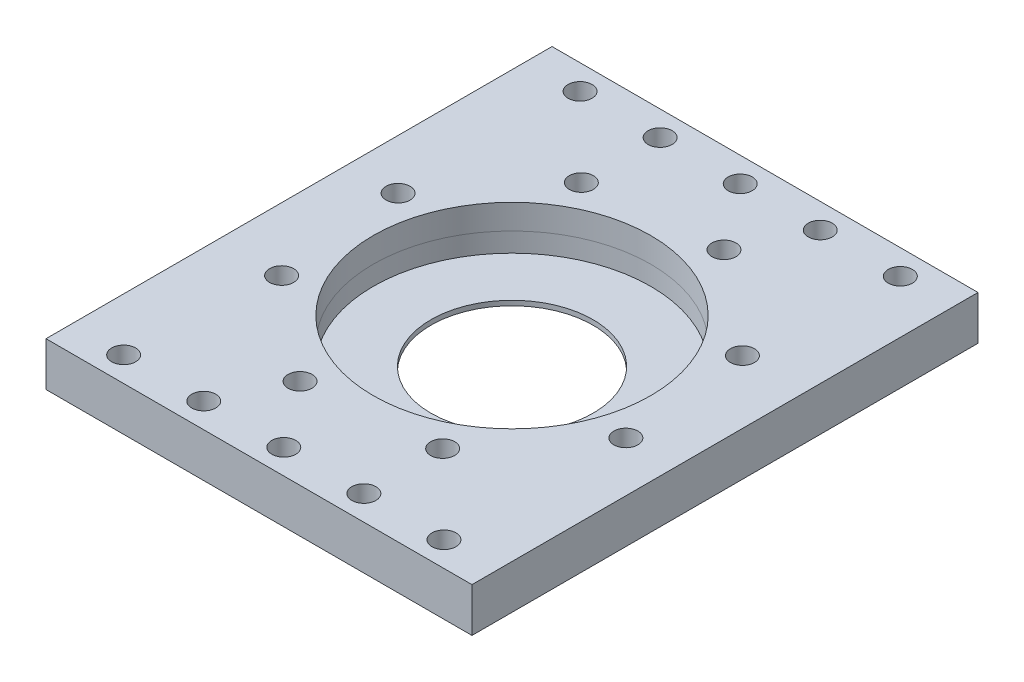
SolidWorks part; units mm, degrees
material "6061-T6 (SS)"
ref_plane "Front Plane" through (0, 0, 0) normal (0, 0, 1) x (1, 0, 0)
ref_plane "Top Plane" through (0, 0, 0) normal (0, 1, 0) x (1, 0, 0)
ref_plane "Right Plane" through (0, 0, 0) normal (1, 0, 0) x (0, 0, -1)
sketch "Sketch1" plane through (0, 0, 0) normal (0, 1, 0) x (1, 0, 0)
  circle A0 centre (0, 0) radius 50
  circle A1 centre (0, 0) radius 20.25
  dimension "D1" = 100
  dimension "D2" = 40.5
extrude "Boss-Extrude1" add sketch "Sketch1" along normal blind 6
sketch "Sketch2" plane through (0, 6, 0) normal (0, 1, 0) x (1, 0, 0)
  line L1 (-20.1161, 37.4379) -> (0, 0) construction
  circle A0 centre (0, 0) radius 42.5 construction
  point P4 (-20.1161, 37.4379)
  point P10 (12.2483, 40.6968)
  point P11 (37.4379, 20.1161)
  point P12 (40.6968, -12.2483)
  point P13 (20.1161, -37.4379)
  point P14 (-12.2483, -40.6968)
  point P15 (-37.4379, -20.1161)
  point P16 (-40.6968, 12.2483)
  dimension "D1" = 85
  dimension "D3" = 28.25
  dimension "D2" = 8
hole_wizard "CBORE for M3 Hex Socket Head Cap Screw2" positions "Sketch2" profile "Sketch3" counterbore size "M3" standard "DIN" end condition through all
sketch "Sketch3" plane through (-40.6968, 6, -12.2483) normal (1, 0, 0) x (0, 0, 1)
  line L0 (0, 0) -> (0, 6)
  line L1 (0, 6) -> (1.7, 6)
  line L3 (1.7, 6) -> (1.7, 3.4)
  line L4 (1.7, 3.4) -> (3.25, 3.4)
  line L5 (3.25, 3.4) -> (3.25, 0)
  line L7 (3.25, 0) -> (0, 0)
  line L11 (0, -6.35) -> (0, 107.95) construction
  dimension "Thru Hole Dia." = 3.4
  dimension "Thru Hole Depth" = 6
  dimension "C'Bore Dia." = 6.5
  dimension "C'Bore Depth" = 3.4
sketch "Sketch6" plane through (0, 6, 0) normal (0, 1, 0) x (1, 0, 0)
  line L0 (-50, 0) -> (-50, -60)
  line L1 (-50, -60) -> (50, -60)
  line L2 (50, -60) -> (50, 0)
  circle A0 centre (0, 0) radius 50 construction
  arc A1 (-50, 0) -> (50, 0) centre (0, 0) ccw
  dimension "D1" = 60
extrude "Boss-Extrude2" add sketch "Sketch6" against normal up to surface (6 mm away) up to face at (-20.1161, 0, -35.7379)
sketch "Sketch10" plane through (0, 6, 0) normal (0, 1, 0) x (1, 0, 0)
  line L0 (-50, 0) -> (-50, 60)
  line L1 (-50, 60) -> (50, 60)
  line L2 (50, 60) -> (50, 0)
  arc A0 (50, 0) -> (-50, 0) centre (0, 0) ccw construction
  arc A1 (50, 0) -> (-50, 0) centre (0, 0) ccw
  dimension "D1" = 60
extrude "Boss-Extrude3" add sketch "Sketch10" against normal up to surface (6 mm away) up to face at (-20.1161, 0, -35.7379)
sketch "Sketch11" plane through (0, 6, 0) normal (0, 1, 0) x (1, 0, 0)
  line L0 (50, 60) -> (-50, 60) construction
  line L3 (0, 0) -> (0, 57) construction
  line L4 (0, 0) -> (-50000, 0) construction
  point P0 (-40, 57)
  point P13 (-20, 57)
  point P14 (0, 57)
  point P15 (20, 57)
  point P16 (40, 57)
  point P57 (40, -57)
  point P58 (20, -57)
  point P59 (0, -57)
  point P60 (-20, -57)
  point P61 (-40, -57)
  dimension "D1" = 3
  dimension "D2" = 5
  dimension "D5" = 20
hole_wizard "CBORE for M3 Hex Socket Head Cap Screw1" positions "Sketch11" profile "Sketch12" counterbore size "M3" standard "DIN" end condition through all
sketch "Sketch12" plane through (-40, 6, -57) normal (1, 0, 0) x (0, 0, 1)
  line L0 (0, 0) -> (0, 6)
  line L1 (0, 6) -> (1.7, 6)
  line L3 (1.7, 6) -> (1.7, 3.4)
  line L4 (1.7, 3.4) -> (3.25, 3.4)
  line L5 (3.25, 3.4) -> (3.25, 0)
  line L7 (3.25, 0) -> (0, 0)
  line L11 (0, -6.35) -> (0, 107.95) construction
  dimension "Thru Hole Dia." = 3.4
  dimension "Thru Hole Depth" = 6
  dimension "C'Bore Dia." = 6.5
  dimension "C'Bore Depth" = 3.4
sketch "Sketch13" plane through (0, 6, 0) normal (0, 1, 0) x (1, 0, 0)
  line L0 (-43.25, 57) -> (-43.25, 60)
  line L1 (-41.25, 60) -> (-50, 60) construction
  line L2 (-43.25, 60) -> (-36.75, 60)
  line L3 (-21.25, 60) -> (-38.75, 60) construction
  line L4 (-36.75, 60) -> (-36.75, 57)
  line L5 (-23.25, 57) -> (-23.25, 60)
  line L6 (-23.25, 60) -> (-16.75, 60)
  line L7 (-16.75, 60) -> (-16.75, 57)
  line L8 (-3.25, 57) -> (-3.25, 60)
  line L9 (-3.25, 60) -> (3.25, 60)
  line L10 (3.25, 60) -> (3.25, 57)
  line L11 (16.75, 57) -> (16.75, 60)
  line L12 (16.75, 60) -> (23.25, 60)
  line L13 (23.25, 60) -> (23.25, 57)
  line L14 (36.75, 57) -> (36.75, 60)
  line L15 (36.75, 60) -> (43.25, 60)
  line L16 (43.25, 60) -> (43.25, 57)
  line L17 (0, 0) -> (69.1463, 0) construction
  line L18 (43.25, -60) -> (43.25, -57)
  line L19 (36.75, -60) -> (43.25, -60)
  line L20 (36.75, -57) -> (36.75, -60)
  line L21 (23.25, -60) -> (23.25, -57)
  line L22 (16.75, -60) -> (23.25, -60)
  line L23 (16.75, -57) -> (16.75, -60)
  line L24 (3.25, -60) -> (3.25, -57)
  line L25 (-3.25, -60) -> (3.25, -60)
  line L26 (-3.25, -57) -> (-3.25, -60)
  line L27 (-16.75, -60) -> (-16.75, -57)
  line L28 (-23.25, -60) -> (-16.75, -60)
  line L29 (-23.25, -57) -> (-23.25, -60)
  line L30 (-36.75, -60) -> (-36.75, -57)
  line L31 (-43.25, -60) -> (-36.75, -60)
  line L32 (-43.25, -57) -> (-43.25, -60)
  arc A0 (-41.25, 60) -> (-38.75, 60) centre (-40, 57) ccw construction
  arc A1 (-43.25, 57) -> (-36.75, 57) centre (-40, 57) ccw
  arc A2 (-23.25, 57) -> (-16.75, 57) centre (-20, 57) ccw
  arc A3 (-3.25, 57) -> (3.25, 57) centre (0, 57) ccw
  arc A4 (16.75, 57) -> (23.25, 57) centre (20, 57) ccw
  arc A5 (36.75, 57) -> (43.25, 57) centre (40, 57) ccw
  arc A6 (36.75, -57) -> (43.25, -57) centre (40, -57) cw
  arc A7 (16.75, -57) -> (23.25, -57) centre (20, -57) cw
  arc A8 (-3.25, -57) -> (3.25, -57) centre (0, -57) cw
  arc A9 (-23.25, -57) -> (-16.75, -57) centre (-20, -57) cw
  arc A10 (-43.25, -57) -> (-36.75, -57) centre (-40, -57) cw
  dimension "D1" = 5
extrude "Cut-Extrude1" cut sketch "Sketch13" against normal up to surface (3.4 mm away) up to face at (-40, 2.6, -56.875)
fillet "Fillet1" radius 1 24 edges at (-43.25, 4.3, 60) (-50, 3, 60) (-50, 3, -60) (-36.75, 4.3, -60) (-23.25, 4.3, -60) (-16.75, 4.3, -60) (-3.25, 4.3, -60) (3.25, 4.3, -60) (16.75, 4.3, -60) (23.25, 4.3, -60) (36.75, 4.3, -60) (43.25, 4.3, -60) (50, 3, -60) (50, 3, 60) (43.25, 4.3, 60) (36.75, 4.3, 60) (23.25, 4.3, 60) (16.75, 4.3, 60) (3.25, 4.3, 60) (-3.25, 4.3, 60) (-16.75, 4.3, 60) (-23.25, 4.3, 60) (-36.75, 4.3, 60) (-43.25, 4.3, -60)
sketch "Sketch15" plane through (0, 6, 0) normal (0, 1, 0) x (1, 0, 0)
  line L0 (0, 0) -> (31.8198, 31.8198) construction
  line L1 (0, 0) -> (31.8198, -31.8198) construction
  line L2 (0, 0) -> (-31.8198, -31.8198) construction
  line L3 (0, 0) -> (-31.8198, 31.8198) construction
  circle A0 centre (0, 0) radius 45
  point P7 (31.8198, 31.8198)
  point P8 (31.8198, -31.8198)
  point P9 (-31.8198, -31.8198)
  point P10 (-31.8198, 31.8198)
  point P11 (0, 0)
  point P19 (-31.8198, 31.8198)
  point P21 (-31.8198, -31.8198)
  point P23 (31.8198, -31.8198)
  dimension "D1" = 90
  dimension "D2" = 45
  dimension "D3" = 4
hole_wizard "Tap Drill for M6 Helicoil1" positions "Sketch15" profile "Sketch16" hole size "M6x1.0" standard "DIN" end condition through all
sketch "Sketch16" plane through (31.8198, 6, 31.8198) normal (1, 0, 0) x (0, 0, 1)
  line L0 (0, 0) -> (0, 6)
  line L1 (0, 6) -> (3.125, 6)
  line L2 (3.125, 6) -> (3.125, 0)
  line L5 (3.125, 0) -> (0, 0)
  line L11 (0, -6.35) -> (0, 107.95) construction
  dimension "Thru Hole Dia." = 6.25
  dimension "Thru Hole Depth" = 6
sketch "Sketch17" plane through (0, 6, 0) normal (0, 1, 0) x (1, 0, 0)
  line L0 (50, -59) -> (50, 59) construction
  line L1 (-50, 60) -> (50, 60) construction
  line L2 (-50, 60) -> (-50, -60) construction
  line L3 (-50, -60) -> (50, -60) construction
  line L4 (50, 60) -> (50, -60) construction
  line L5 (-50, 59) -> (-50, -59) construction
  line L6 (-35.75, -60) -> (-24.25, -60) construction
  line L7 (-24.25, 60) -> (-35.75, 60) construction
  line L8 (-50.2, 60.2) -> (-50.2, -60.2)
  line L9 (-50.2, -60.2) -> (50.2, -60.2)
  line L10 (50.2, 60.2) -> (50.2, -60.2)
  line L11 (-50.2, 60.2) -> (50.2, 60.2)
  dimension "D1" = 0.2
extrude "Boss-Extrude4" add sketch "Sketch17" along normal blind 6.2 separate body
sketch "Sketch18" plane through (0, 6, 0) normal (0, -1, 0) x (1, 0, 0)
  line L0 (-53.2, -63.2) -> (53.2, -63.2)
  line L1 (53.2, -63.2) -> (53.2, 63.2)
  line L2 (53.2, 63.2) -> (-53.2, 63.2)
  line L3 (-53.2, 63.2) -> (-53.2, -63.2)
  line L4 (-50.2, -60.2) -> (50.2, -60.2)
  line L5 (50.2, -60.2) -> (50.2, 60.2)
  line L6 (50.2, 60.2) -> (-50.2, 60.2)
  line L7 (-50.2, 60.2) -> (-50.2, -60.2)
  line L8 (-50.2, -60.2) -> (50.2, -60.2)
  line L9 (50.2, -60.2) -> (50.2, 60.2)
  line L10 (50.2, 60.2) -> (-50.2, 60.2)
  line L11 (-50.2, 60.2) -> (-50.2, -60.2)
  dimension "D1" = 0
  dimension "D2" = 3
extrude "Boss-Extrude5" add sketch "Sketch18" along normal blind 11 from surface starting at face at (0, 12.2, 0)
sketch "Sketch21" plane through (0, 6, 0) normal (0, -1, 0) x (-1, 0, 0)
  point P0 (-40, 57)
  point P3 (-20, 57)
  point P6 (0, 57)
  point P9 (20, 57)
  point P12 (40, 57)
  point P15 (20.1161, 37.4379)
  point P18 (40.6968, 12.2483)
  point P21 (-12.2483, 40.6968)
  point P24 (-37.4379, 20.1161)
  point P27 (-40.6968, -12.2483)
  point P30 (-20.1161, -37.4379)
  point P33 (12.2483, -40.6968)
  point P36 (37.4379, -20.1161)
  point P39 (40, -57)
  point P42 (20, -57)
  point P45 (0, -57)
  point P48 (-20, -57)
  point P51 (-40, -57)
hole_wizard "Ø6.0mm Dowel Hole1" positions "Sketch21" profile "Sketch20" hole size "Ø6.0" standard "DIN" end condition through all
sketch "Sketch20" plane through (40, 6, -57) normal (1, 0, 0) x (0, 0, -1)
  line L0 (0, 0) -> (0, 6.2)
  line L1 (0, 6.2) -> (3, 6.2)
  line L2 (3, 6.2) -> (3, 0)
  line L5 (3, 0) -> (0, 0)
  line L11 (0, -6.35) -> (0, 107.95) construction
  dimension "Thru Hole Dia." = 6
  dimension "Thru Hole Depth" = 6.2
sketch "Sketch22" plane through (0, 12.2, 0) normal (0, 1, 0) x (1, 0, 0)
  circle A0 centre (0, 0) radius 34.6516
extrude "Cut-Extrude2" cut sketch "Sketch22" against normal blind 11
